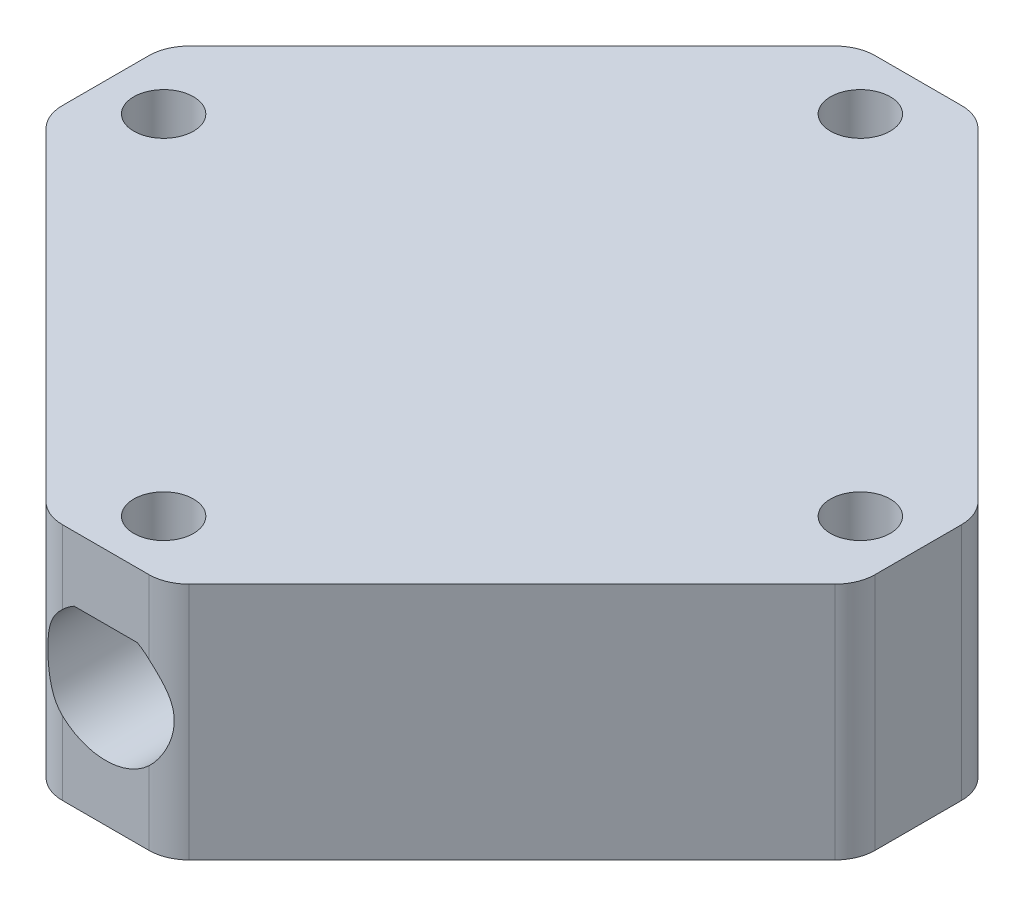
SolidWorks part; units mm, degrees
material "Nylon 101"
ref_plane "Front Plane" through (0, 0, 0) normal (0, 0, 1) x (1, 0, 0)
ref_plane "Top Plane" through (0, 0, 0) normal (0, 1, 0) x (1, 0, 0)
ref_plane "Right Plane" through (0, 0, 0) normal (1, 0, 0) x (0, 0, -1)
sketch "Sketch1" plane through (0, 0, 0) normal (0, 1, 0) x (1, 0, 0)
  line L0 (-20.41, -20.41) -> (20.41, 20.41) construction
  line L1 (-3, -20.41) -> (3, -20.41)
  line L2 (-20.41, -3) -> (-20.41, 3)
  line L3 (-3, 20.41) -> (3, 20.41)
  line L4 (20.41, -3) -> (20.41, 3)
  line L5 (20.41, 3) -> (3, 20.41)
  line L6 (3, -20.41) -> (20.41, -3)
  line L7 (-20.41, -3) -> (-3, -20.41)
  line L8 (-3, 20.41) -> (-20.41, 3)
  point P4 (0, 0)
  point P17 (0, 0)
  dimension "D1" = 3
  dimension "D2" = 20.41
  dimension "D3" = 4
extrude "Boss-Extrude1" add sketch "Sketch1" along normal blind 12
sketch "Sketch2" plane through (0, 0, 20.41) normal (0, 0, 1) x (1, 0, 0)
  line L0 (20.41, 12) -> (20.41, 0) construction
  line L1 (1.5875, 8.7496) -> (-1.5875, 8.7496)
  arc A1 (-1.5875, 8.7496) -> (1.5875, 8.7496) centre (0, 6) ccw
  point P7 (20.41, 6)
  dimension "D1" = 3.175
  dimension "D2" = 3.175
sketch "Sketch3" plane through (0, 12, 0) normal (0, 1, 0) x (1, 0, 0)
  line L1 (0, 0) -> (17.5, 0) construction
  circle A0 centre (17.5, 0) radius 1.5
  circle A1 centre (0, -17.5) radius 1.5
  circle A2 centre (-17.5, 0) radius 1.5
  circle A3 centre (0, 17.5) radius 1.5
  point P13 (0, 0)
  dimension "D2" = 3
  dimension "D1" = 17.5
  dimension "D3" = 4
extrude "Cut-Extrude1" cut sketch "Sketch3" against normal blind 3
extrude "Cut-Extrude2" cut sketch "Sketch2" against normal blind 25.4 contours L1 A1
fillet "Fillet1" radius 2 8 edges at (-20.41, 6, 3) (-20.41, 6, -3) (-3, 6, -20.41) (3, 6, -20.41) (20.41, 6, -3) (20.41, 6, 3) (3, 2.4802, 20.41) (-3, 9.5198, 20.41)
